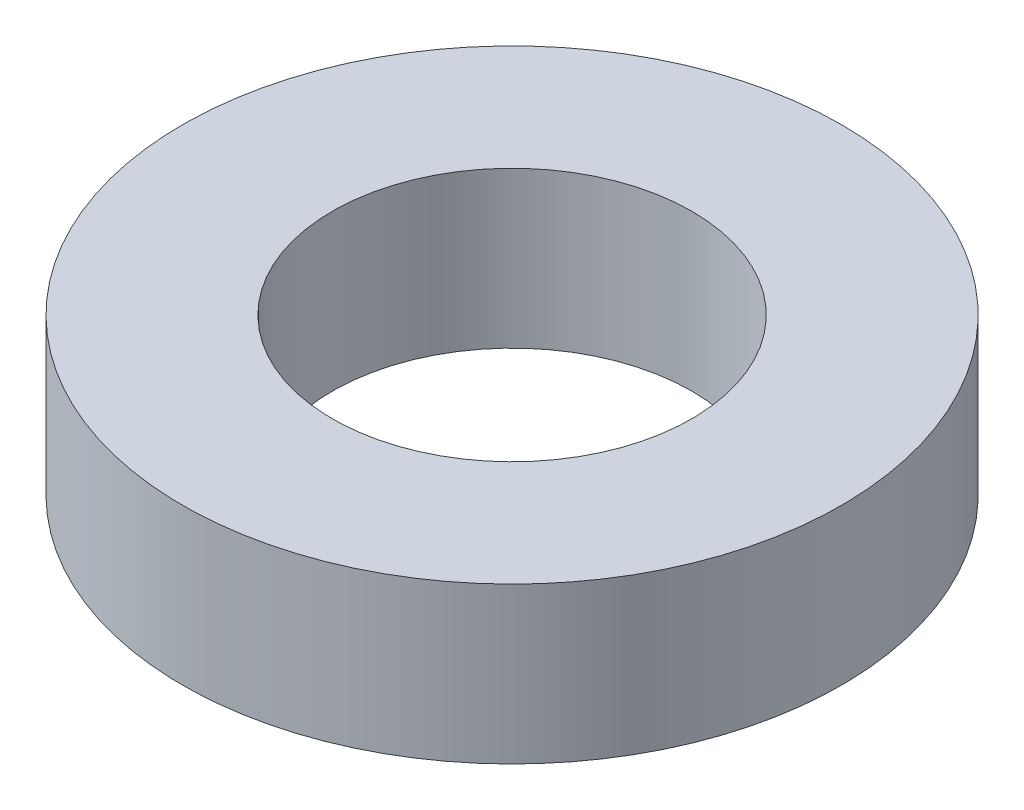
SolidWorks part; units mm, degrees
ref_plane "Front Plane" through (0, 0, 0) normal (0, 0, 1) x (1, 0, 0)
ref_plane "Top Plane" through (0, 0, 0) normal (0, 1, 0) x (1, 0, 0)
ref_plane "Right Plane" through (0, 0, 0) normal (1, 0, 0) x (0, 0, -1)
sketch "Sketch1" plane through (0, 0, 0) normal (0, 1, 0) x (1, 0, 0)
  circle A0 centre (0, 0) radius 27.5
  dimension "FLANGE_OD" = 55
extrude "Boss-Extrude1" add sketch "Sketch1" along normal blind 13
sketch "Sketch2" plane through (0, 0, 0) normal (0, 1, 0) x (1, 0, 0)
  circle A0 centre (0, 0) radius 15
  dimension "BORE_D" = 30
extrude "Cut-Extrude1" cut sketch "Sketch2" along normal through all
sketch "Sketch3" plane through (0, 13, 0) normal (0, 1, 0) x (1, 0, 0)
  circle A0 centre (0, 0) radius 9.2151 construction
  circle A1 centre (-9.2151, 0) radius 1.562
  dimension "BOLT_D" = 3.124
  dimension "BOLT_PCD" = 18.4302
extrude "Cut-Extrude2" cut sketch "Sketch3" against normal blind 9.2664 rebuild error yes
pattern_circular "CirPattern1" count 4 over 360 rebuild error yes
